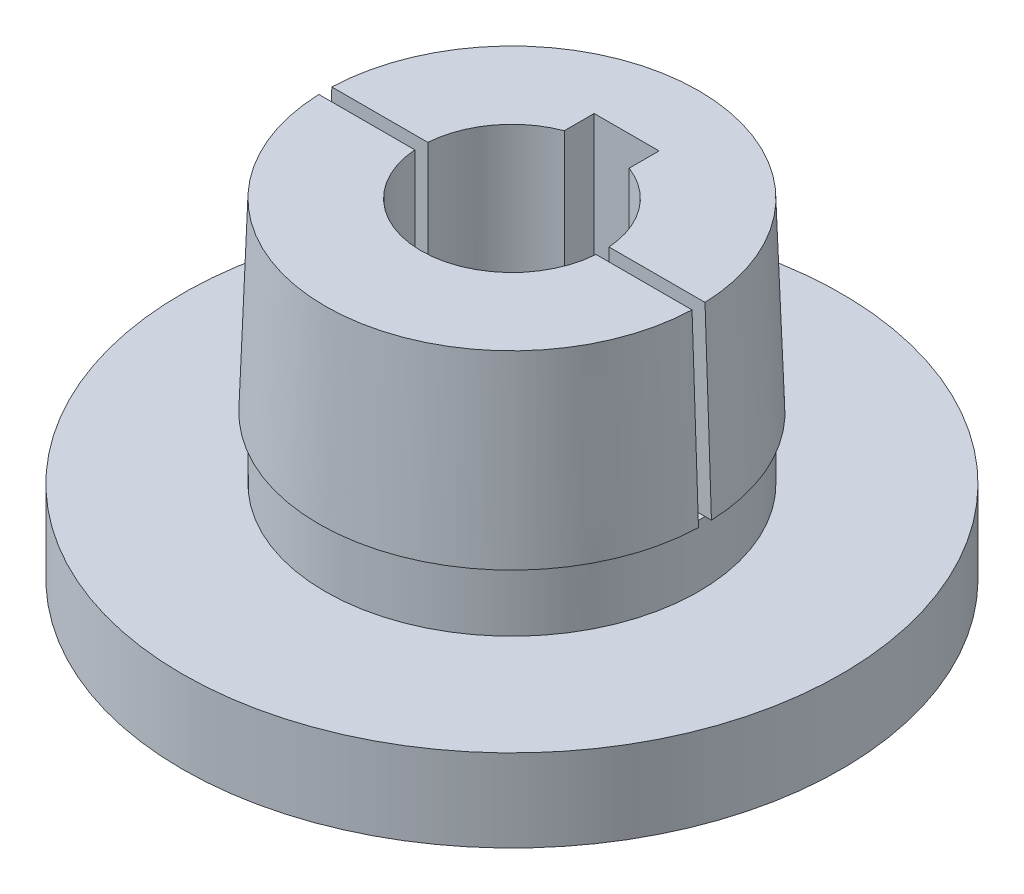
SolidWorks part; units mm, degrees
ref_plane "Front Plane" through (0, 0, 0) normal (0, 0, 1) x (1, 0, 0)
ref_plane "Top Plane" through (0, 0, 0) normal (0, 1, 0) x (1, 0, 0)
ref_plane "Right Plane" through (0, 0, 0) normal (1, 0, 0) x (0, 0, -1)
sketch "Sketch1" plane through (0, 0, 0) normal (0, 0, 1) x (1, 0, 0)
  line L0 (0, 0) -> (25.4, 0)
  line L1 (25.4, 0) -> (25.4, 6.35)
  line L2 (25.4, 6.35) -> (14.3891, 6.35)
  line L3 (14.3891, 6.35) -> (14.3891, 11.1125)
  line L4 (14.3891, 11.1125) -> (14.8844, 11.1125)
  line L5 (14.8844, 11.1125) -> (14.3891, 25.4)
  line L6 (14.3891, 25.4) -> (0, 25.4)
  line L7 (0, 25.4) -> (0, 0)
  point P7 (0, 0)
  point P10 (0, 0)
  point P11 (0, 0)
  dimension "D1" = 25.4
  dimension "D2" = 25.4
  dimension "D3" = 6.35
  dimension "D4" = 14.3891
  dimension "D5" = 14.8844
  dimension "D6" = 4.7625
revolve "Revolve1" add sketch "Sketch1" angle 360 about L7
sketch "Sketch2" plane through (0, 25.4, 0) normal (0, 1, 0) x (1, 0, 0)
  line L2 (-2.5, 6.5383) -> (-2.5, 8.8383)
  line L3 (-2.5, 8.8383) -> (2.5, 8.8383)
  line L4 (2.5, 6.5383) -> (2.5, 8.8383)
  line L5 (-2.5, 6.5383) -> (2.5, 8.8383) construction
  line L6 (-2.5, 8.8383) -> (2.5, 6.5383) construction
  arc A0 (-2.5, 6.5383) -> (2.5, 6.5383) centre (0, 0) ccw
  point P7 (0, 7.6883)
  point P8 (0, 0)
  point P9 (0, 8.8383)
  point P10 (1.3742, 6.8638)
  dimension "D1" = 14
  dimension "D2" = 5
  dimension "D3" = 2.3
extrude "Cut-Extrude1" cut sketch "Sketch2" against normal through all
sketch "Sketch4" plane through (0, 25.4, 0) normal (0, 1, 0) x (1, 0, 0)
  line L0 (-14.8844, 0) -> (0, 0) construction
  line L1 (-14.8844, 0.5) -> (14.8844, 0.5)
  line L2 (-14.8844, 0.5) -> (-14.8844, -0.5)
  line L3 (-14.8844, -0.5) -> (14.8844, -0.5)
  line L4 (14.8844, 0.5) -> (14.8844, -0.5)
  line L5 (-14.8844, 0.5) -> (14.8844, -0.5) construction
  line L6 (-14.8844, -0.5) -> (14.8844, 0.5) construction
  point P4 (0, 0)
  dimension "D1" = 1
  dimension "D2" = 14.8844
extrude "Cut-Extrude2" cut sketch "Sketch4" against normal up to surface (14.2875 mm away) up to face at (0, 11.1125, 14.8844)
sketch "Sketch6" plane through (0, 6.35, 0) normal (0, 1, 0) x (1, 0, 0)
  line L0 (0, 0) -> (17.9605, 17.9605) construction
  circle A0 centre (18.2617, 9.0576) radius 3.175
  circle A2 centre (0, 0) radius 25.4 construction
  dimension "D1" = 6.35
